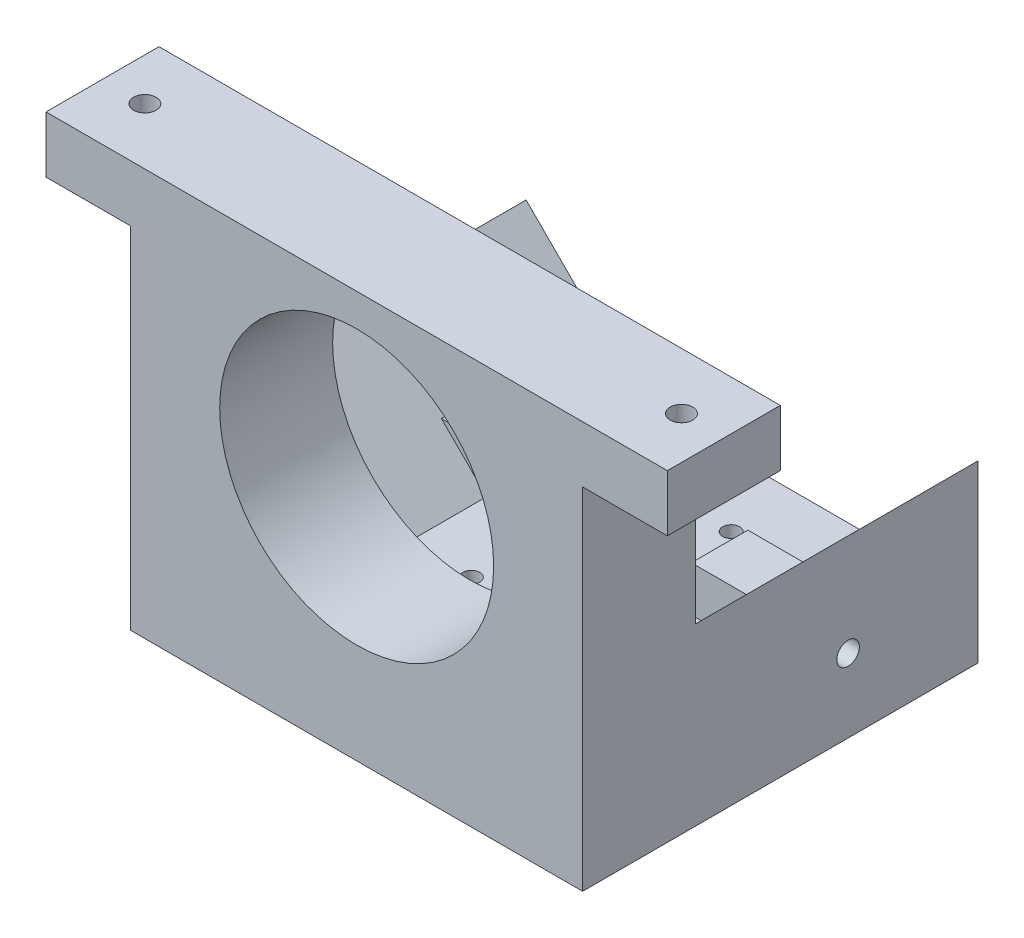
SolidWorks part; units mm, degrees
ref_plane "Front Plane" through (0, 0, 0) normal (0, 0, 1) x (1, 0, 0)
ref_plane "Top Plane" through (0, 0, 0) normal (0, 1, 0) x (1, 0, 0)
ref_plane "Right Plane" through (0, 0, 0) normal (1, 0, 0) x (0, 0, -1)
sketch "Sketch1" plane through (0, 0, 0) normal (0, 0, 1) x (1, 0, 0)
  line L1 (-40, -30) -> (40, -30)
  line L2 (-40, -30) -> (-40, 30)
  line L3 (-40, 30) -> (40, 30)
  line L4 (40, -30) -> (40, 30)
  line L5 (-40, -30) -> (40, 30) construction
  line L6 (-40, 30) -> (40, -30) construction
  circle A0 centre (0, 0) radius 24.25
  dimension "D1" = 48.5
  dimension "D2" = 80
  dimension "D3" = 60
extrude "Boss-Extrude1" add sketch "Sketch1" along normal blind 20
sketch "Sketch4" plane through (40, 0, 0) normal (1, 0, 0) x (0, 0, -1)
  line L0 (0, -30) -> (0, 30) construction
  line L1 (-20, 30) -> (0, 30)
  line L2 (-20, 30) -> (-20, 20)
  line L3 (-20, 20) -> (0, 20)
  line L4 (0, 30) -> (0, 20)
  line L5 (-20, 30) -> (0, 20) construction
  line L6 (-20, 20) -> (0, 30) construction
  point P4 (-10, 25)
  dimension "D1" = 10
extrude "Boss-Extrude3" add sketch "Sketch4" along normal blind 15
sketch "Sketch5" plane through (0, 30, 0) normal (0, 1, 0) x (1, 0, 0)
  line L0 (55, -10) -> (-40, -10) construction
  line L1 (55, 0) -> (55, -20) construction
  line L2 (-40, -20) -> (-40, 0) construction
  line L3 (40, 0) -> (40, -20) construction
  line L4 (55, 0) -> (-40, 0) construction
  line L5 (55, -20) -> (-40, -20) construction
  circle A0 centre (47.5, -10) radius 2
  dimension "D1" = 4
  dimension "D2" = 7.5
extrude "Cut-Extrude2" cut sketch "Sketch5" against normal up to surface (10 mm away) up to face at (47.5, 20, 10)
sketch "Sketch6" plane through (0, -30, 0) normal (0, -1, 0) x (-1, 0, 0)
  line L1 (40, -20) -> (-40, -20)
  line L2 (40, -20) -> (40, 0)
  line L3 (40, 0) -> (-40, 0)
  line L4 (-40, -20) -> (-40, 0)
  line L5 (40, -20) -> (-40, 0) construction
  line L6 (40, 0) -> (-40, -20) construction
  point P4 (0, -10)
extrude "Boss-Extrude4" add sketch "Sketch6" along normal blind 2
sketch "Sketch8" plane through (0, 0, 0) normal (0, 0, -1) x (-1, 0, 0)
  line L0 (-40, -11) -> (-19, -32)
  line L1 (-40, -32) -> (-40, 20) construction
  line L2 (40, -32) -> (-40, -32) construction
  line L3 (-19, -32) -> (-40, -32)
  line L4 (-40, -32) -> (-40, -11)
  dimension "D1" = 21
extrude "Boss-Extrude6" add sketch "Sketch8" along normal blind 50
sketch "Sketch9" plane through (40, 0, 0) normal (1, 0, 0) x (0, 0, -1)
  line L0 (-20, -32) -> (-20, 20) construction
  line L1 (50, -32) -> (-20, -32) construction
  circle A0 centre (27, -29) radius 2
  dimension "D1" = 4
  dimension "D2" = 47
  dimension "D3" = 3
extrude "Cut-Extrude3" cut sketch "Sketch9" against normal through all
ref_plane "Plane1" through (19, 0, 0) normal (-1, 0, 0) x (0, 0, 1)
sketch "Sketch10" plane through (19, 0, 0) normal (-1, 0, 0) x (0, 0, 1)
  line L0 (-50, -32) -> (0, -32) construction
  line L1 (-32, -32) -> (-22, -32)
  line L2 (-32, -32) -> (-32, -24)
  line L3 (-32, -24) -> (-22, -24)
  line L4 (-22, -32) -> (-22, -24)
  line L5 (-32, -32) -> (-22, -24) construction
  line L6 (-32, -24) -> (-22, -32) construction
  circle A2 centre (-27, -29) radius 2 construction
  point P4 (-27, -28)
  dimension "D1" = 8
  dimension "D2" = 10
extrude "Boss-Extrude7" add sketch "Sketch10" along normal blind 1.75 and the other way up to surface other way up to face at (24, -27, -27)
sketch "Sketch11" plane through (17.25, 0, 0) normal (-1, 0, 0) x (0, 0, 1)
  circle A0 centre (-27, -29) radius 2
  circle A1 centre (-27, -29) radius 2 construction
extrude "Cut-Extrude4" cut sketch "Sketch11" against normal up to surface (22.75 mm away) up to face at (40, -29, -29)
fillet "Fillet1" radius 0.001 2 edges at (17.25, -28, -22) (17.25, -28, -32)
sketch "Sketch12" plane through (0, -32, 0) normal (0, -1, 0) x (1, 0, 0)
  line L0 (0, 20) -> (0, -50) construction
  line L1 (-40, 20) -> (40, 20)
  line L2 (-40, 20) -> (-40, -50)
  line L3 (-40, -50) -> (40, -50)
  line L4 (40, 20) -> (40, -50)
  line L5 (-40, 20) -> (40, -50) construction
  line L6 (-40, -50) -> (40, 20) construction
  line L7 (-8, -8.3) -> (8, -8.3) construction
  line L8 (-8, -8.3) -> (-8, -38.3) construction
  line L9 (-8, -38.3) -> (8, -38.3) construction
  line L10 (8, -38.3) -> (8, -8.3) construction
  line L11 (-40, 0) -> (19, 0) construction
  circle A0 centre (-8, -8.3) radius 1.5
  circle A1 centre (8, -8.3) radius 1.5
  circle A2 centre (8, -38.3) radius 1.5
  circle A3 centre (-8, -38.3) radius 1.5
  point P4 (0, -15)
  point P11 (0, -8.3)
  dimension "D4" = 3
  dimension "D1" = 16
  dimension "D2" = 30
  dimension "D3" = 8.3
extrude "Boss-Extrude8" add sketch "Sketch12" along normal blind 10
ref_plane "Plane2" through (0, 0, 0) normal (1, 0, 0) x (0, 0, -1)
mirror "Mirror1" about plane through (0, 0, 0) normal (1, 0, 0) of "Fillet1", "Cut-Extrude4", "Boss-Extrude7", "Cut-Extrude3", "Boss-Extrude6", "Boss-Extrude4", "Cut-Extrude2", "Boss-Extrude3"
